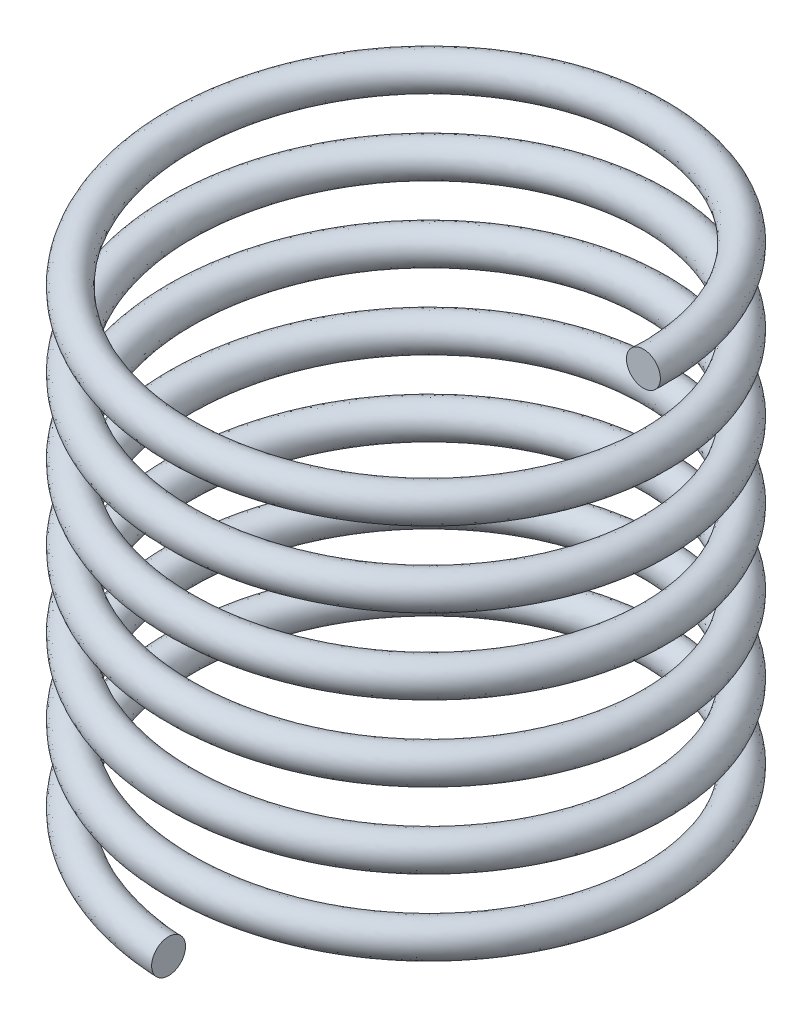
SolidWorks part; units mm, degrees
note: '?' marks a value the reader was unsure of.
material "AISI Type 316L stainless steel"
ref_plane "Front Plane" through (0, 0, 0) normal (0, 0, 1) x (1, 0, 0)
ref_plane "Top Plane" through (0, 0, 0) normal (0, 1, 0) x (1, 0, 0)
ref_plane "Right Plane" through (0, 0, 0) normal (1, 0, 0) x (0, 0, -1)
sketch "Sketch2" plane through (0, 0, 0) normal (0, 1, 0) x (1, 0, 0)
  circle A0 centre (0, 0) radius 3.5
  dimension "D1" = 7
curve "Helix/Spiral2" pitch 1.1111 height 7.5 turns 6.75
sketch "Sketch3" plane through (0, 0, 0) normal (1, 0, 0) x (0, 0, -1)
  circle A0 centre (-3.5, 0) radius 0.25
  spline S0 degree 3 poles (-3.5, 0) (-3.5, 0.023) (-3.3178, 0.0695) (-2.5393, 0.1389) (-1.3743, 0.2083) (0, 0.2778) (1.3743, 0.3472) (2.5393, 0.4167) (3.3178, 0.4861) (3.5911, 0.5556) (3.3178, 0.625) (2.5393, 0.6944) (1.3743, 0.7639) (0, 0.8333) (-1.3743, 0.9028) (-2.5393, 0.9722) (-3.3178, 1.0417) (-3.5911, 1.1111) (-3.3178, 1.1806) (-2.5393, 1.25) (-1.3743, 1.3194) (0, 1.3889) (1.3743, 1.4583) (2.5393, 1.5278) (3.3178, 1.5972) (3.5911, 1.6667) (3.3178, 1.7361) (2.5393, 1.8056) (1.3743, 1.875) (0, 1.9444) (-1.3743, 2.0139) (-2.5393, 2.0833) (-3.3178, 2.1528) (-3.5911, 2.2222) (-3.3178, 2.2917) (-2.5393, 2.3611) (-1.3743, 2.4306) (0, 2.5) (1.3743, 2.5694) (2.5393, 2.6389) (3.3178, 2.7083) (3.5911, 2.7778) (3.3178, 2.8472) (2.5393, 2.9167) (1.3743, 2.9861) (0, 3.0556) (-1.3743, 3.125) (-2.5393, 3.1944) (-3.3178, 3.2639) (-3.5911, 3.3333) (-3.3178, 3.4028) (-2.5393, 3.4722) (-1.3743, 3.5417) (0, 3.6111) (1.3743, 3.6806) (2.5393, 3.75) (3.3178, 3.8194) (3.5911, 3.8889) (3.3178, 3.9583) (2.5393, 4.0278) (1.3743, 4.0972) (0, 4.1667) (-1.3743, 4.2361) (-2.5393, 4.3056) (-3.3178, 4.375) (-3.5911, 4.4444) (-3.3178, 4.5139) (-2.5393, 4.5833) (-1.3743, 4.6528) (0, 4.7222) (1.3743, 4.7917) (2.5393, 4.8611) (3.3178, 4.9306) (3.5911, 5) (3.3178, 5.0694) (2.5393, 5.1389) (1.3743, 5.2083) (0, 5.2778) (-1.3743, 5.3472) (-2.5393, 5.4167) (-3.3178, 5.4861) (-3.5911, 5.5556) (-3.3178, 5.625) (-2.5393, 5.6944) (-1.3743, 5.7639) (0, 5.8333) (1.3743, 5.9028) (2.5393, 5.9722) (3.3178, 6.0417) (3.5911, 6.1111) (3.3178, 6.1806) (2.5393, 6.25) (1.3743, 6.3194) (0, 6.3889) (-1.3743, 6.4583) (-2.5393, 6.5278) (-3.3178, 6.5972) (-3.5911, 6.6667) (-3.3178, 6.7361) (-2.5393, 6.8056) (-1.3743, 6.875) (0, 6.9444) (1.3743, 7.0139) (2.5393, 7.0833) (3.3178, 7.1528) (3.5911, 7.2222) (3.3179, 7.2917) (2.5389, 7.3611) (1.3756, 7.4305) (0.4552, 7.477) (0, 7.5) knots 0 0 0 0 0.009259 0.018519 0.027778 0.037037 0.046296 0.055556 0.064815 0.074074 0.083333 0.092593 0.101852 0.111111 0.12037 0.12963 0.138889 0.148148 0.157407 0.166667 0.175926 0.185185 0.194444 0.203704 0.212963 0.222222 0.231481 0.240741 0.25 0.259259 0.268519 0.277778 0.287037 0.296296 0.305556 0.314815 0.324074 0.333333 0.342593 0.351852 0.361111 0.37037 0.37963 0.388889 0.398148 0.407407 0.416667 0.425926 0.435185 0.444444 0.453704 0.462963 0.472222 0.481481 0.490741 0.5 0.509259 0.518519 0.527778 0.537037 0.546296 0.555556 0.564815 0.574074 0.583333 0.592593 0.601852 0.611111 0.62037 0.62963 0.638889 0.648148 0.657407 0.666667 0.675926 0.685185 0.694444 0.703704 0.712963 0.722222 0.731481 0.740741 0.75 0.759259 0.768519 0.777778 0.787037 0.796296 0.805556 0.814815 0.824074 0.833333 0.842593 0.851852 0.861111 0.87037 0.87963 0.888889 0.898148 0.907407 0.916667 0.925926 0.935185 0.944444 0.953704 0.962963 0.972222 0.981481 0.990741 1 1 1 1 construction
  dimension "D1" = 0.5
sweep "Sweep1" add profiles "Sketch3" path "Helix/Spiral2"
sketch "Sketch4" plane through (0, 0, 0) normal (0, 0, 1) x (1, 0, 0)
  line L0 (0, 0) -> (0, 8)
ref_axis "Axis1" through (0, 0, 0) along (0, 1, 0)?
